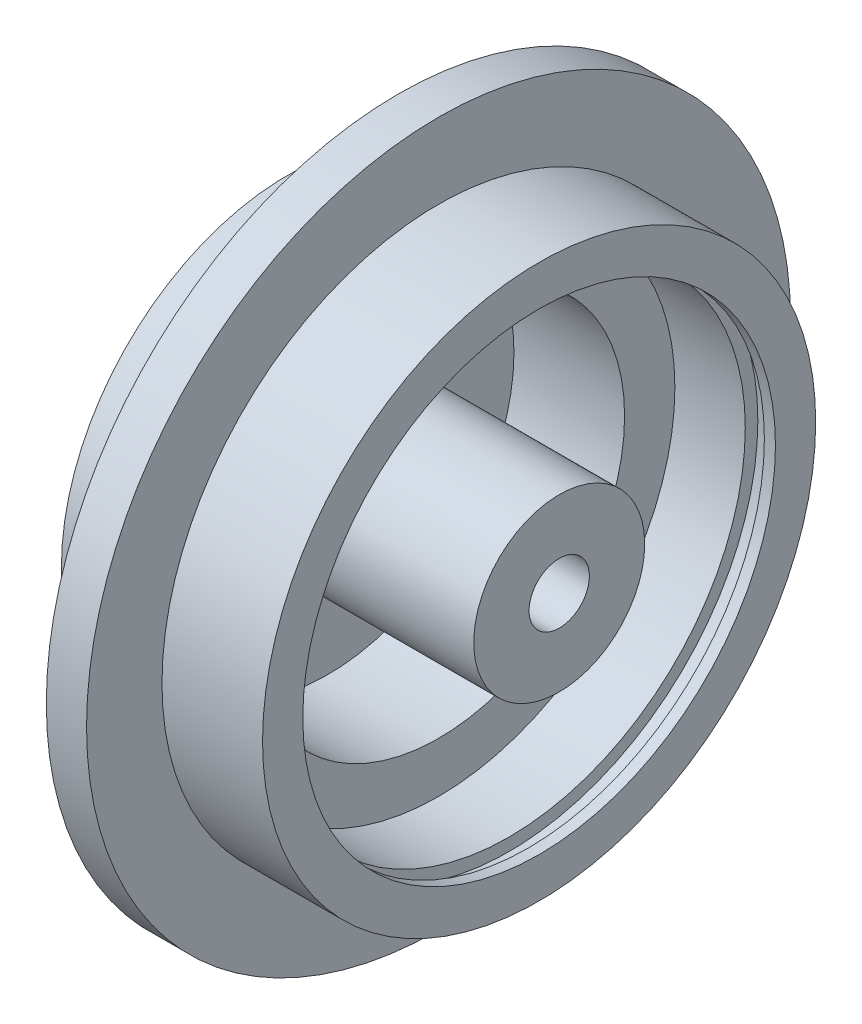
SolidWorks part; units mm, degrees
ref_plane "Front Plane" through (0, 0, 0) normal (0, 0, 1) x (1, 0, 0)
ref_plane "Top Plane" through (0, 0, 0) normal (0, 1, 0) x (1, 0, 0)
ref_plane "Right Plane" through (0, 0, 0) normal (1, 0, 0) x (0, 0, -1)
sketch "Sketch1" plane through (0, 0, 0) normal (1, 0, 0) x (0, 0, -1)
  circle A0 centre (0, 0) radius 35
extrude "Boss-Extrude1" add sketch "Sketch1" along normal blind 27
sketch "Sketch2" plane through (0, 0, 0) normal (-1, 0, 0) x (0, 0, 1)
  circle A0 centre (0, 0) radius 3
extrude "Cut-Extrude1" cut sketch "Sketch2" against normal up to next
sketch "Sketch3" plane through (27, 0, 0) normal (1, 0, 0) x (0, 0, -1)
  circle A0 centre (0, 0) radius 8.5
  circle A1 centre (0, 0) radius 18.5
extrude "Cut-Extrude2" cut sketch "Sketch3" against normal blind 23
sketch "Sketch4" plane through (27, 0, 0) normal (1, 0, 0) x (0, 0, -1)
  circle A0 centre (0, 0) radius 23.5
  circle A1 centre (0, 0) radius 18.5
extrude "Cut-Extrude5" cut sketch "Sketch4" against normal blind 12
sketch "Sketch6" plane through (0, 0, 0) normal (-1, 0, 0) x (0, 0, 1)
  circle A0 centre (0, 0) radius 22.5
  circle A1 centre (0, 0) radius 35.0333
extrude "Cut-Extrude6" cut sketch "Sketch6" against normal blind 11
sketch "Sketch7" plane through (27, 0, 0) normal (1, 0, 0) x (0, 0, -1)
  circle A0 centre (0, 0) radius 35
  circle A1 centre (0, 0) radius 27.5
extrude "Cut-Extrude7" cut sketch "Sketch7" against normal blind 12
sketch "Sketch8" plane through (27, 0, 0) normal (1, 0, 0) x (0, 0, -1)
  circle A0 centre (0, 0) radius 35
  circle A1 centre (0, 0) radius 8.5
extrude "Cut-Extrude8" cut sketch "Sketch8" against normal blind 2
ref_plane "Plane5" through (22.95, 0, 0) normal (1, 0, 0) x (0, 0, -1)
sketch "Sketch9" plane through (22.95, 0, 0) normal (1, 0, 0) x (0, 0, -1)
  circle A0 centre (0, 0) radius 24.75
  circle A1 centre (0, 0) radius 8.5
extrude "Cut-Extrude13" cut sketch "Sketch9" against normal mid plane 1.9
sketch "Sketch10" plane through (15, 0, 0) normal (1, 0, 0) x (0, 0, -1)
  circle A0 centre (28.33, 0) radius 3
  dimension "D1" = 28.33
